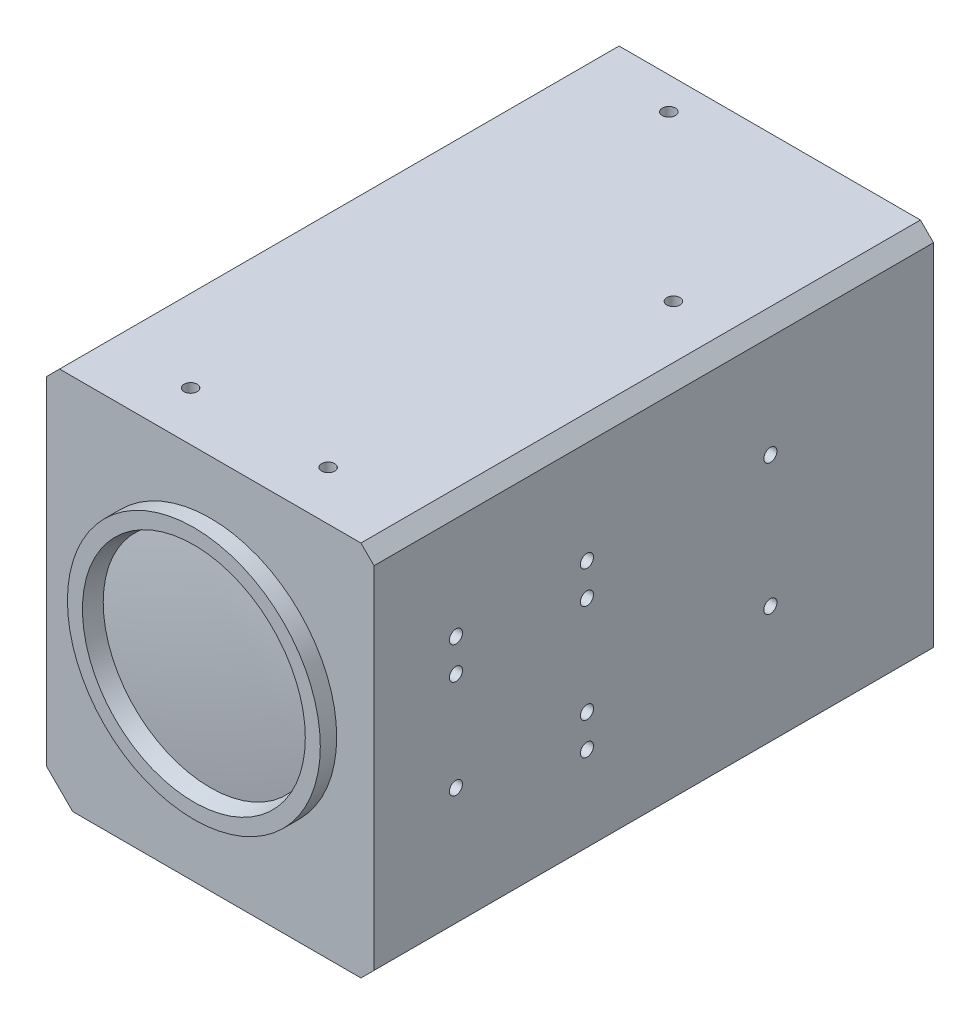
SolidWorks part; units mm, degrees
ref_plane "Front Plane" through (0, 0, 0) normal (0, 0, 1) x (1, 0, 0)
ref_plane "Top Plane" through (0, 0, 0) normal (0, 1, 0) x (1, 0, 0)
ref_plane "Right Plane" through (0, 0, 0) normal (1, 0, 0) x (0, 0, -1)
sketch "Sketch1" plane through (0, 0, 0) normal (0, 0, 1) x (1, 0, 0)
  line L0 (-25, 25.5) -> (-23, 27.5)
  line L1 (-21, -30) -> (23, -30)
  line L2 (-25, -26) -> (-25, 25.5)
  line L3 (-23, 27.5) -> (23, 27.5)
  line L4 (25, -28) -> (25, 25.5)
  line L5 (23, 27.5) -> (25, 25.5)
  line L6 (23, -30) -> (25, -28)
  line L7 (-25, -26) -> (-21, -30)
  point P0 (0, 0)
  point P1 (25, 27.5)
  point P2 (-25, -30)
  point P3 (-25, 27.5)
  point P4 (25, -30)
  dimension "D1" = 57.5
  dimension "D2" = 50
  dimension "D3" = 30
  dimension "D4" = 25
extrude "Boss-Extrude1" add sketch "Sketch1" along normal blind 85.4
sketch "Sketch2" plane through (0, 0, 85.4) normal (0, 0, 1) x (1, 0, 0)
  circle A0 centre (0, 0) radius 19.3
  circle A1 centre (0, 0) radius 17.008
  dimension "D1" = 38.6
  dimension "D2" = 34.016
extrude "Boss-Extrude2" add sketch "Sketch2" along normal blind 2.5
draft "Draft1" type of draft neutral plane draft angle 15 faces to draft 1 face at (17.008, 0, 87.9) neutral plane through (0, 0, 87.9) neutral plane normal (0, 0, 1) parameters "D1"=15
dome "Dome1" faces to dome 1 distance 1 reverse direction no elliptical dome no face at (-16.3381, 0, 85.4) parameters "D1"=1
hole_wizard "Ø2.0 (2) Diameter Hole1" positions "3DSketch1" profile "Sketch3" hole size "Ø2.0" standard "Ansi Metric"
sketch3d "3DSketch1"
  line L0 (25, 9.8997, 85.4) -> (25, 9.8997, 24.9) construction
  line L1 (25, -28, 85.4) -> (25, 25.5, 85.4) construction
  line L4 (25, -10.1003, 85.4) -> (25, -10.1003, 24.9) construction
  line L10 (25, 4.9428, 85.4) -> (25, 4.9428, 52.9) construction
  line L12 (23, -30, 85.4) -> (23, -30, 0) construction
  line L13 (-21, -30, 85.4) -> (-21, -30, 0) construction
  line L14 (0, 27.5, 0) -> (0, 27.5, 85.4) construction
  line L15 (23, 27.5, 0) -> (-23, 27.5, 0) construction
  line L16 (23, 27.5, 85.4) -> (-23, 27.5, 85.4) construction
  line L18 (-10.5, 27.5, 77.9) -> (10.5, 27.5, 77.9) construction
  line L20 (10.5, 27.5, 77.9) -> (10.5, 27.5, 29.6) construction
  line L21 (10.5, 27.5, 29.6) -> (14.9, 27.5, 29.6) construction
  line L22 (0, -30, 85.4) -> (0, -30, 0) construction
  line L23 (-21, -30, 85.4) -> (23, -30, 85.4) construction
  line L24 (-21, -30, 0) -> (23, -30, 0) construction
  point P0 (25, 9.8997, 72.9)
  point P2 (25, 9.8997, 52.9)
  point P4 (25, 4.9428, 72.9)
  point P6 (25, -10.1003, 72.9)
  point P8 (25, 4.9428, 52.9)
  point P10 (25, -10.1003, 52.9)
  point P12 (25, -15.0572, 52.9)
  point P14 (25, 9.8997, 24.9)
  point P16 (25, -10.1003, 24.9)
  point P64 (-25, -9.7327, 2.7)
  point P66 (-25, 4.2673, 2.7)
  point P72 (-10.5, 27.5, 77.9)
  point P74 (10.5, 27.5, 77.9)
  point P76 (14.9, 27.5, 29.6)
  point P78 (-10.5, 27.5, 4.9)
  point P107 (8, -30, 22.9)
  point P109 (-8, -30, 22.9)
  point P111 (-8, -30, 51.9)
  point P113 (8, -30, 51.9)
  point P115 (13.5, -30, 47.7)
  point P117 (-13.5, -30, 47.7)
  point P119 (13.5, -30, 14.7)
  point P121 (-13.5, -30, 14.7)
  dimension "D1" = 20
  dimension "D2" = 20
  dimension "D3" = 15
  dimension "D4" = 28
  dimension "D5" = 20
  dimension "D6" = 35
  dimension "D13" = 10
  dimension "D14" = 73
  dimension "D15" = 48.3
  dimension "D16" = 4.4
  dimension "D17" = 25
  dimension "D18" = 36
  dimension "D19" = 40.2
  dimension "D20" = 16
  dimension "D21" = 8
  dimension "D22" = 27
  dimension "D23" = 13.5
  dimension "D24" = 29
  dimension "D25" = 33
  dimension "D7" = 20
  dimension "D8" = 85.2
  dimension "D9" = 14
  dimension "D10" = 34.5
  dimension "D11" = 21
  dimension "D12" = 10.5
sketch "Sketch3" plane through (25, 9.8997, 72.9) normal (0, 1, 0) x (0, 0, -1)
  line L0 (0, 0) -> (0, 4.6009)
  line L1 (0, 4.6009) -> (1, 4)
  line L2 (1, 4) -> (1, 0)
  line L5 (1, 0) -> (0, 0)
  line L10 (0, 4.6009) -> (-1, 4) construction
  line L11 (0, -6.35) -> (0, 107.95) construction
  dimension "Hole Dia." = 2
  dimension "Hole Depth" = 4
  dimension "Drill Angle" = 118
hole_wizard "1/4 Clearance Hole1" positions "Sketch5" profile "Sketch4" hole size "1/4" standard "Ansi Inch"
sketch "Sketch5" plane through (0, -30, 0) normal (0, -1, 0) x (1, 0, 0)
  line L0 (25, 85.4) -> (25, 0) construction
  line L1 (19.3, 87.9) -> (-19.3, 87.9) construction
  point P0 (0, 67.9)
  dimension "D1" = 25
  dimension "D2" = 20
sketch "Sketch4" plane through (0, -30, 67.9) normal (1, 0, 0) x (0, 0, -1)
  line L0 (0, 0) -> (0, 10.0298)
  line L1 (0, 10.0298) -> (3.3782, 8)
  line L2 (3.3782, 8) -> (3.3782, 0)
  line L5 (3.3782, 0) -> (0, 0)
  line L10 (0, 10.0298) -> (-3.3782, 8) construction
  line L11 (0, -6.35) -> (0, 107.95) construction
  dimension "Hole Dia." = 6.7564
  dimension "Hole Depth" = 8
  dimension "Drill Angle" = 118
